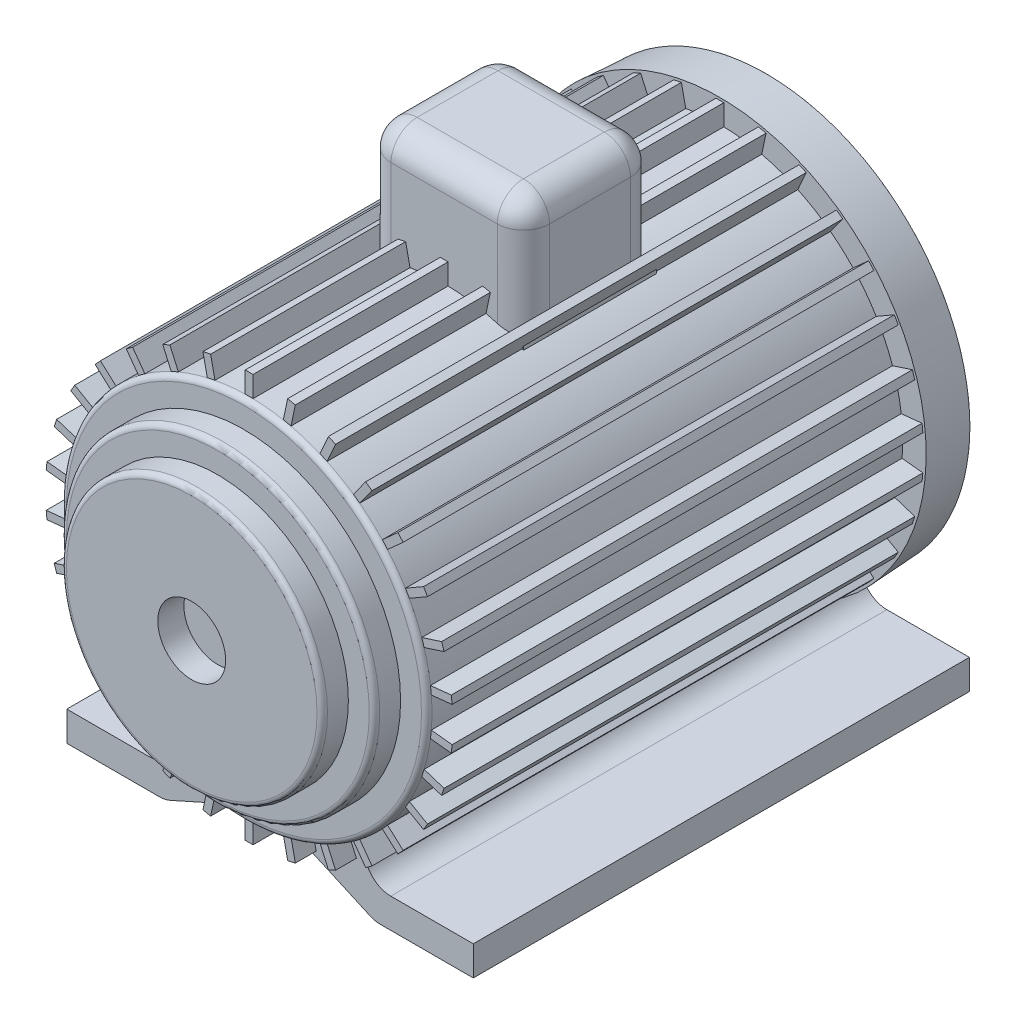
SolidWorks part; units mm, degrees
material "1023 Carbon Steel Sheet (SS)"
ref_plane "Front Plane" through (0, 0, 0) normal (0, 0, 1) x (1, 0, 0)
ref_plane "Top Plane" through (0, 0, 0) normal (0, 1, 0) x (1, 0, 0)
ref_plane "Right Plane" through (0, 0, 0) normal (1, 0, 0) x (0, 0, -1)
sketch "Sketch1" plane through (0, 0, 0) normal (0, 0, 1) x (1, 0, 0)
  circle A0 centre (0, 0) radius 70
extrude "Boss-Extrude2" add sketch "Sketch1" along normal blind 200
sketch "Sketch2" plane through (0, 0, 200) normal (0, 0, 1) x (1, 0, 0)
  circle A0 centre (0, 0) radius 60
extrude "Boss-Extrude3" add sketch "Sketch2" along normal blind 10
sketch "Sketch3" plane through (0, 0, 210) normal (0, 0, 1) x (1, 0, 0)
  circle A0 centre (0, 0) radius 50
extrude "Boss-Extrude4" add sketch "Sketch3" along normal blind 10
fillet "Fillet1" radius 2 3 edges at (70, 0, 200) (50, 0, 220) (60, 0, 210)
sketch "Sketch4" plane through (0, 0, 220) normal (0, 0, 1) x (1, 0, 0)
  circle A0 centre (0, 0) radius 13
extrude "Cut-Extrude1" cut sketch "Sketch4" against normal blind 10
sketch "Sketch5" plane through (0, 0, 0) normal (0, 0, -1) x (-1, 0, 0)
  line L0 (0, -70) -> (0, -94.8666) construction
  line L1 (-32.5074, -61.9941) -> (-40.1917, -76.6487)
  line L2 (-40.1917, -76.6487) -> (-77.8393, -76.6487)
  line L3 (-77.8393, -76.6487) -> (-77.8393, -87.9984)
  line L4 (-77.8393, -87.9984) -> (-40.1917, -87.9984)
  line L5 (-40.1917, -87.9984) -> (0, -70)
  line L6 (77.8393, -87.9984) -> (40.1917, -87.9984)
  line L7 (77.8393, -76.6487) -> (77.8393, -87.9984)
  line L8 (40.1917, -76.6487) -> (77.8393, -76.6487)
  line L9 (32.5074, -61.9941) -> (40.1917, -76.6487)
  line L10 (40.1917, -87.9984) -> (0, -70)
  circle A0 centre (0, 0) radius 70 construction
  arc A1 (-32.5074, -61.9941) -> (32.5074, -61.9941) centre (0, 0) ccw
  circle M7 centre (0, 0) radius 70
extrude "Boss-Extrude5" add sketch "Sketch5" against normal blind 190 contours L4 L5 L1 L2 L3 M7 | L10 L6 L7 L8 L9 M7 region at (42.2112, -78.1515, 0) region at (-42.2112, -78.1515, 0)
fillet "Fillet2" radius 10 7 edges at (32.5074, -61.9941, 95) (-32.5074, -61.9941, 95) (40.1917, -87.9984, 95) (-40.1917, -87.9984, 95) (-40.1917, -76.6487, 95) (0, -70, 95) (40.1917, -76.6487, 95)
sketch "Sketch6" plane through (0, 0, 0) normal (1, 0, 0) x (0, 0, -1)
  line L0 (-198, 70) -> (-198, 78)
  line L1 (-198, 78) -> (0, 78)
  line L2 (0, 78) -> (0, 70)
  line L3 (-198, 70) -> (-198, 66.1548)
  line L4 (-198, -70) -> (-198, 70) construction
  line L5 (-198, 66.1548) -> (0, 66.1548)
  line L6 (0, -57.4445) -> (0, 70) construction
  line L7 (0, 66.1548) -> (0, 70)
extrude "Boss-Extrude6" add sketch "Sketch6" along normal mid plane 3
pattern_circular "CirPattern1" count 30 over 360 about axis through (0, 0, 200) along (0, 0, -1) of "Boss-Extrude6" reverse direction yes
sketch "Sketch7" plane through (0, 0, 0) normal (0, 1, 0) x (1, 0, 0)
  line L0 (0, -198) -> (0, 0) construction
  line L1 (30.3551, -123.3037) -> (-30.3551, -123.3037)
  line L2 (30.3551, -123.3037) -> (30.3551, -72.3375)
  line L3 (30.3551, -72.3375) -> (-30.3551, -72.3375)
  line L4 (-30.3551, -123.3037) -> (-30.3551, -72.3375)
  line L5 (30.3551, -123.3037) -> (-30.3551, -72.3375) construction
  line L6 (30.3551, -72.3375) -> (-30.3551, -123.3037) construction
  line L7 (-30.3551, 0) -> (-30.3551, -198) construction
  point P0 (0, -97.8206)
extrude "Boss-Extrude7" add sketch "Sketch7" along normal blind 110
fillet "Fillet3" radius 10 4 edges at (0, 110, 72.3375) (30.3551, 110, 97.8206) (0, 110, 123.3037) (-30.3551, 110, 97.8206)
fillet "Fillet4" radius 10 8 edges at (27.4262, 107.0711, 120.3747) (-27.4262, 107.0711, 120.3747) (-27.4262, 107.0711, 75.2664) (27.4262, 107.0711, 75.2664) (30.3551, 85.9333, 123.3037) (-30.3551, 85.9333, 123.3037) (-30.3551, 85.9333, 72.3375) (30.3551, 85.9333, 72.3375)
sketch "Sketch8" plane through (0, 0, 0) normal (1, 0, 0) x (0, 0, -1)
  line L1 (0, -5.8235) -> (0, 5.8235) construction
  line L3 (-17.7095, 78.9958) -> (-17.7095, 0)
  line L4 (-17.7095, 0) -> (0, 0)
  line L6 (0, 78) -> (-17.7095, 78.9958)
  line L7 (0, 78) -> (3.4363, 69.5458)
  line L8 (3.4363, 69.5458) -> (3.4363, 0)
  line L9 (3.4363, 0) -> (0, 0)
revolve "Revolve3" add sketch "Sketch8" angle 360 about L4
